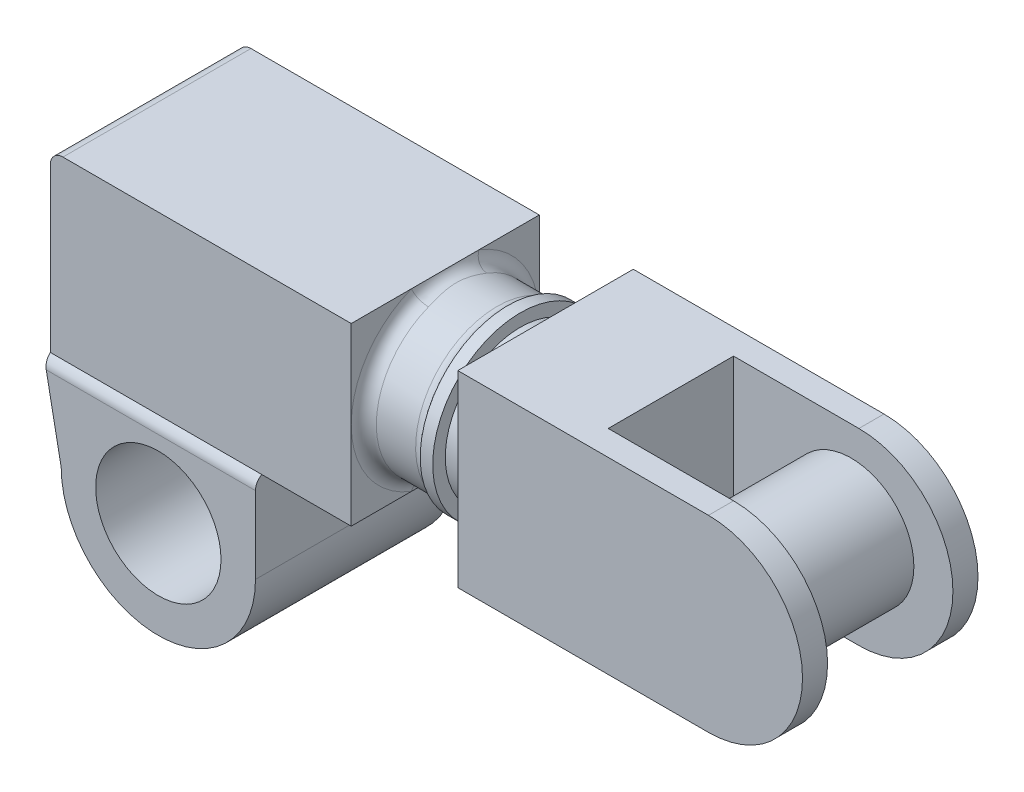
SolidWorks part; units mm, degrees
ref_plane "Front Plane" through (0, 0, 0) normal (0, 0, 1) x (1, 0, 0)
ref_plane "Top Plane" through (0, 0, 0) normal (0, 1, 0) x (1, 0, 0)
ref_plane "Right Plane" through (0, 0, 0) normal (1, 0, 0) x (0, 0, -1)
sketch "Sketch1" plane through (0, 0, 0) normal (1, 0, 0) x (0, 0, -1)
  line L1 (-75, 70) -> (75, 70)
  line L2 (-75, 70) -> (-75, -70)
  line L3 (-75, -70) -> (75, -70)
  line L4 (75, 70) -> (75, -70)
  line L5 (-75, 70) -> (75, -70) construction
  line L6 (-75, -70) -> (75, 70) construction
  point P0 (0, 0)
  dimension "D1" = 140
  dimension "D2" = 150
extrude "Boss-Extrude1" add sketch "Sketch1" along normal blind 240
sketch "Sketch2" plane through (240, 0, 0) normal (1, 0, 0) x (0, 0, -1)
  circle A0 centre (0, 0) radius 65
  dimension "D1" = 130
extrude "Boss-Extrude2" add sketch "Sketch2" along normal blind 50
sketch "Sketch3" plane through (290, 0, 0) normal (1, 0, 0) x (0, 0, -1)
  circle A0 centre (0, 0) radius 70
  dimension "D1" = 140
extrude "Boss-Extrude3" add sketch "Sketch3" along normal blind 10
sketch "Sketch4" plane through (0, 0, 0) normal (0, 0, 1) x (1, 0, 0)
  line L0 (168.6066, -140) -> (168.6066, -70)
  line L1 (240, -70) -> (0, -70) construction
  line L2 (13.6066, -140) -> (0, -70)
  line L3 (0, 70) -> (0, -70) construction
  line L4 (168.6066, -70) -> (0, -70)
  arc A0 (13.6066, -140) -> (168.6066, -140) centre (91.1066, -140) ccw
  circle A1 centre (91.1066, -140) radius 50
  dimension "D2" = 155
  dimension "D6" = 100
  dimension "D1" = 70
  dimension "D3" = 191
extrude "Boss-Extrude5" add sketch "Sketch4" along normal mid plane 160
fillet "Fillet1" radius 10 4 edges at (240, 0, -65) (290, 0, -65) (84.3033, -70, 80) (84.3033, -70, -75)
fillet "Fillet2" radius 10 1 edges at (0, 70, 0)
sketch "Sketch5" plane through (300, 0, 0) normal (1, 0, 0) x (0, 0, -1)
  circle A0 centre (0, 0) radius 60
  dimension "D1" = 120
extrude "Boss-Extrude6" add sketch "Sketch5" along normal blind 20
sketch "Sketch6" plane through (0, 0, 0) normal (0, 0, 1) x (1, 0, 0)
  line L0 (520, -75) -> (320, -75)
  line L1 (320, -75) -> (320, 75)
  line L2 (320, 75) -> (520, 75)
  line L3 (320, -60) -> (320, 60) construction
  arc A0 (520, -75) -> (520, 75) centre (520, 0) ccw
  dimension "D1" = 150
  dimension "D2" = 200
extrude "Boss-Extrude10" add sketch "Sketch6" along normal mid plane 140
ref_plane "Plane5" through (0, 0, 10) normal (0, 0, 1) x (1, 0, 0)
sketch "Sketch12" plane through (0, 0, 10) normal (0, 0, 1) x (1, 0, 0)
  line L0 (520, 75) -> (420, 75)
  line L1 (520, 75) -> (320, 75) construction
  line L2 (420, 75) -> (420, -75)
  line L3 (320, -75) -> (520, -75) construction
  line L4 (420, -75) -> (520, -75)
  arc A0 (520, -75) -> (520, 75) centre (520, 0) ccw construction
  arc A1 (520, -75) -> (520, 75) centre (520, 0) ccw
extrude "Cut-Extrude2" cut sketch "Sketch12" against normal blind 60
sketch "Sketch14" plane through (0, 0, 10) normal (0, 0, 1) x (1, 0, 0)
  line L0 (520, 75) -> (420, 75)
  line L1 (520, 75) -> (320, 75) construction
  line L2 (420, 75) -> (420, -75)
  line L3 (420, -75) -> (520, -75)
  arc A0 (520, -75) -> (520, 75) centre (520, 0) ccw construction
  arc A1 (520, -75) -> (520, 75) centre (520, 0) ccw
extrude "Cut-Extrude3" cut sketch "Sketch14" along normal blind 40
sketch "Sketch15" plane through (0, 0, 10) normal (0, 0, 1) x (1, 0, 0)
  circle A0 centre (516.357, 3.9855) radius 50
  dimension "D1" = 100
extrude "Boss-Extrude11" add sketch "Sketch15" along normal mid plane 115
